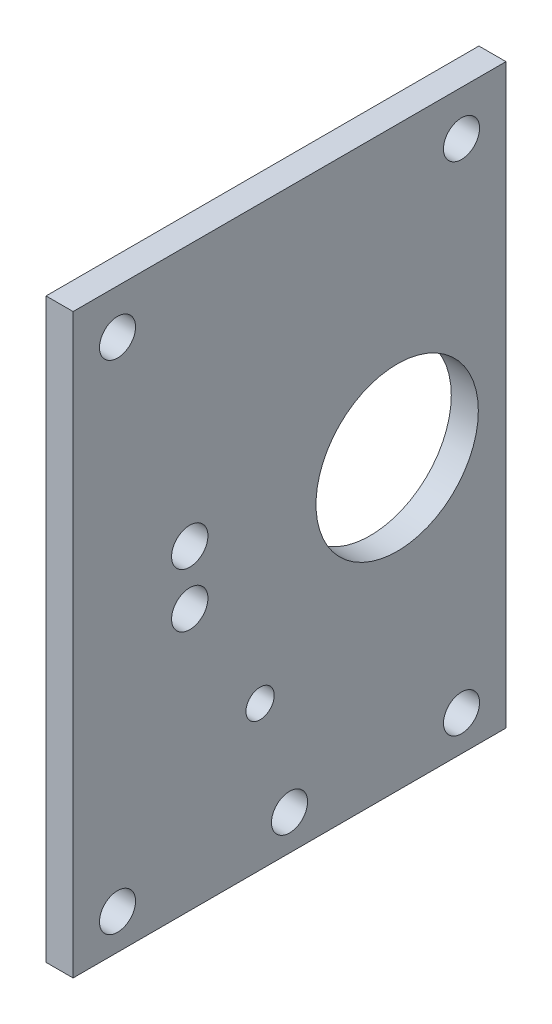
SolidWorks part; units mm, degrees
material "6061 Alloy"
ref_plane "Front Plane" through (0, 0, 0) normal (0, 0, 1) x (1, 0, 0)
ref_plane "Top Plane" through (0, 0, 0) normal (0, 1, 0) x (1, 0, 0)
ref_plane "Right Plane" through (0, 0, 0) normal (1, 0, 0) x (0, 0, -1)
sketch "Sketch2" plane through (0, 0, 0) normal (1, 0, 0) x (0, 0, -1)
  line L1 (-38.1, -50.8) -> (38.1, -50.8)
  line L2 (-38.1, -50.8) -> (-38.1, 50.8)
  line L3 (-38.1, 50.8) -> (38.1, 50.8)
  line L4 (38.1, -50.8) -> (38.1, 50.8)
  line L5 (-38.1, -50.8) -> (38.1, 50.8) construction
  line L6 (-38.1, 50.8) -> (38.1, -50.8) construction
  point P0 (0, 0)
  dimension "D1" = 76.2
  dimension "D2" = 101.6
extrude "Boss-Extrude1" add sketch "Sketch2" along normal blind 4.7625
sketch "Sketch3" plane through (4.7625, 0, 0) normal (1, 0, 0) x (0, 0, -1)
  line L5 (30.2768, -44.5643) -> (-30.2768, -44.5643) construction
  line L6 (-30.2768, 42.9768) -> (30.2768, 42.9768) construction
  line L7 (30.2768, 42.9768) -> (30.2768, -44.5643) construction
  line L8 (-30.2768, 42.9768) -> (-30.2768, -44.5643) construction
  line L9 (-38.1, 50.8) -> (-38.1, -50.8) construction
  line L10 (38.1, 50.8) -> (-38.1, 50.8) construction
  line L11 (38.1, -50.8) -> (38.1, 50.8) construction
  line L12 (-38.1, -50.8) -> (38.1, -50.8) construction
  circle A0 centre (30.2768, -44.5643) radius 3.175
  circle A1 centre (30.2768, 42.9768) radius 3.175
  circle A2 centre (-30.2768, 42.9768) radius 3.175
  circle A3 centre (-30.2768, -44.5643) radius 3.175
  circle A4 centre (18.9484, 0) radius 14.2875
  circle A5 centre (-5.1816, -25.4) radius 2.4892
  circle A6 centre (0, -44.5643) radius 3.175
  dimension "D1" = 6.35
  dimension "D5" = 7.8232
  dimension "D7" = 7.8232
  dimension "D8" = 6.2357
  dimension "D9" = 28.575
  dimension "D10" = 50.8
  dimension "D11" = 4.9784
  dimension "D12" = 25.4
  dimension "D6" = 7.8232
  dimension "D13" = 24.13
  dimension "D14" = 19.1516
extrude "Cut-Extrude1" cut sketch "Sketch3" against normal blind 6.35 contours A1
extrude "Cut-Extrude2" cut sketch "Sketch3<4>" against normal blind 6.35
sketch "Sketch3<4>" plane through (4.7625, 0, 0) normal (1, 0, 0) x (0, 0, -1) same geometry as "Sketch3"
hole_wizard "M6 Clearance Hole1" positions "Sketch5" profile "Sketch4" hole size "M6" standard "ANSI Metric" end condition up to next
sketch "Sketch5" plane through (4.7625, 0, 0) normal (1, 0, 0) x (0, 0, -1)
  circle A0 centre (-17.5641, 4.7625) radius 1.65 construction
  circle A1 centre (-17.5641, -4.7625) radius 1.65 construction
  point P0 (-17.5641, -4.7625)
  point P2 (-17.5641, 4.7625)
sketch "Sketch4" plane through (4.7625, -4.7625, 17.5641) normal (0, 1, 0) x (0, 0, -1)
  line L0 (0, 0) -> (0, 4.7625)
  line L1 (0, 4.7625) -> (3.2, 4.7625)
  line L2 (3.2, 4.7625) -> (3.2, 0)
  line L5 (3.2, 0) -> (0, 0)
  line L11 (0, -6.35) -> (0, 107.95) construction
  dimension "Thru Hole Dia." = 6.4
  dimension "Thru Hole Depth" = 4.7625
